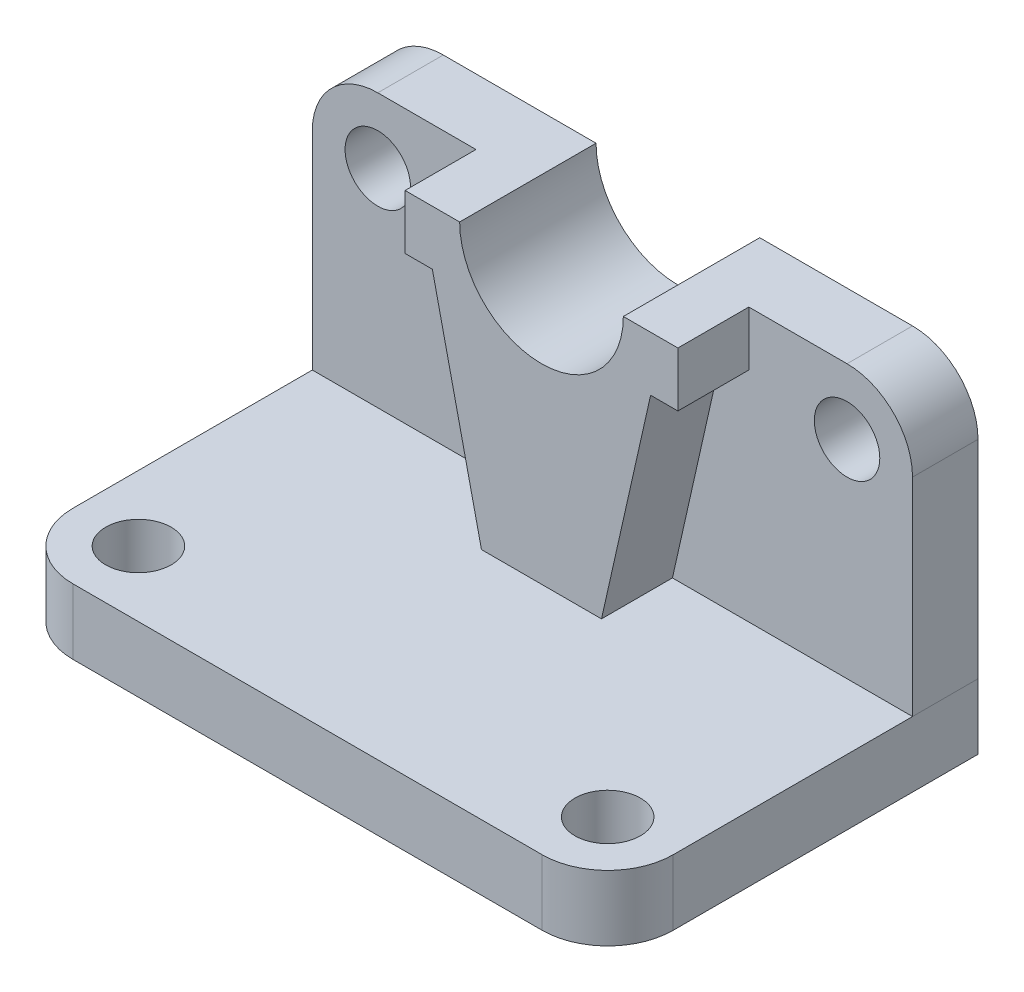
SolidWorks part; units mm, degrees
material "1060 Alloy"
ref_plane "Front Plane" through (0, 0, 0) normal (0, 0, 1) x (1, 0, 0)
ref_plane "Top Plane" through (0, 0, 0) normal (0, 1, 0) x (1, 0, 0)
ref_plane "Right Plane" through (0, 0, 0) normal (1, 0, 0) x (0, 0, -1)
sketch "Sketch2" plane through (0, 0, 0) normal (0, 1, 0) x (1, 0, 0)
  line L1 (-12, -67.8683) -> (-98, -67.8683)
  line L2 (0, -55.8683) -> (0, 0)
  line L3 (0, 0) -> (-110, 0)
  line L4 (-110, -55.8683) -> (-110, 0)
  arc A0 (-12, -67.8683) -> (0, -55.8683) centre (-12, -55.8683) ccw
  arc A1 (-110, -55.8683) -> (-98, -67.8683) centre (-98, -55.8683) ccw
  circle A2 centre (-98, -55.8683) radius 6
  circle A3 centre (-12, -55.8683) radius 6
  dimension "D3" = 24
  dimension "D6" = 24
  dimension "D1" = 12
  dimension "D2" = 12
  dimension "D4" = 12
  dimension "D5" = 12
  dimension "D7" = 12
  dimension "D8" = 12
  dimension "D9" = 110
  dimension "D10" = 0
  dimension "D11" = 0
extrude "Boss-Extrude1" add sketch "Sketch2" along normal blind 12 contours A3 | A2 | L4 L3 L2 A0 L1 A1
sketch "Sketch14" plane through (0, 0, 0) normal (0, 0, 1) x (1, 0, 0)
  line L0 (-80, 62) -> (-80, 52)
  line L1 (0, 0) -> (-110, 0)
  line L2 (0, 0) -> (0, 50)
  line L4 (-110, 0) -> (-110, 50)
  line L5 (-80, 52) -> (-75, 52)
  line L6 (-75, 52) -> (-66, 12)
  line L7 (-12, 12) -> (-98, 12) construction
  line L8 (-66, 12) -> (-44, 12)
  line L9 (-35, 52) -> (-30, 52)
  line L10 (-30, 52) -> (-30, 62)
  line L11 (-44, 12) -> (-35, 52)
  line L12 (-66, 12) -> (-110, 12)
  line L14 (-98, 62) -> (-80, 62)
  line L15 (-80, 62) -> (-70, 62)
  line L16 (-40, 62) -> (-30, 62)
  line L17 (-30, 62) -> (-12, 62)
  line L18 (-44, 12) -> (0, 12)
  arc A0 (-98, 62) -> (-110, 50) centre (-98, 50) ccw
  arc A1 (0, 50) -> (-12, 62) centre (-12, 50) ccw
  circle A2 centre (-98, 50) radius 6
  circle A3 centre (-12, 50) radius 6
  arc A4 (-70, 62) -> (-40, 62) centre (-55, 62) ccw
  dimension "D3" = 24
  dimension "D6" = 24
  dimension "D2" = 12
  dimension "D9" = 12
  dimension "D1" = 110
  dimension "D4" = 12
  dimension "D7" = 12
  dimension "D10" = 30
  dimension "D11" = 50
  dimension "D12" = 25
  dimension "D13" = 10
  dimension "D14" = 10
  dimension "D15" = 22
  dimension "D16" = 40
  dimension "D17" = 44
  dimension "D18" = 5
extrude "Boss-Extrude9" add sketch "Sketch14" along normal blind 12 separate body contours L14 A0 L4 L12 L6 L5 L0 A2 | L2 A1 L17 L10 L9 L11 L18 A3 region at (-90.1843, 33.97, 0) region at (-19.8157, 33.97, 0)
extrude "Boss-Extrude10" add sketch "Sketch14<8>" along normal blind 25 contours A4 L15 L0 L5 L6 L8 L11 L9 L10 L16 region at (-55, 36.7218, 0)
sketch "Sketch14<8>" plane through (0, 0, 0) normal (0, 0, 1) x (1, 0, 0) same geometry as "Sketch14"
